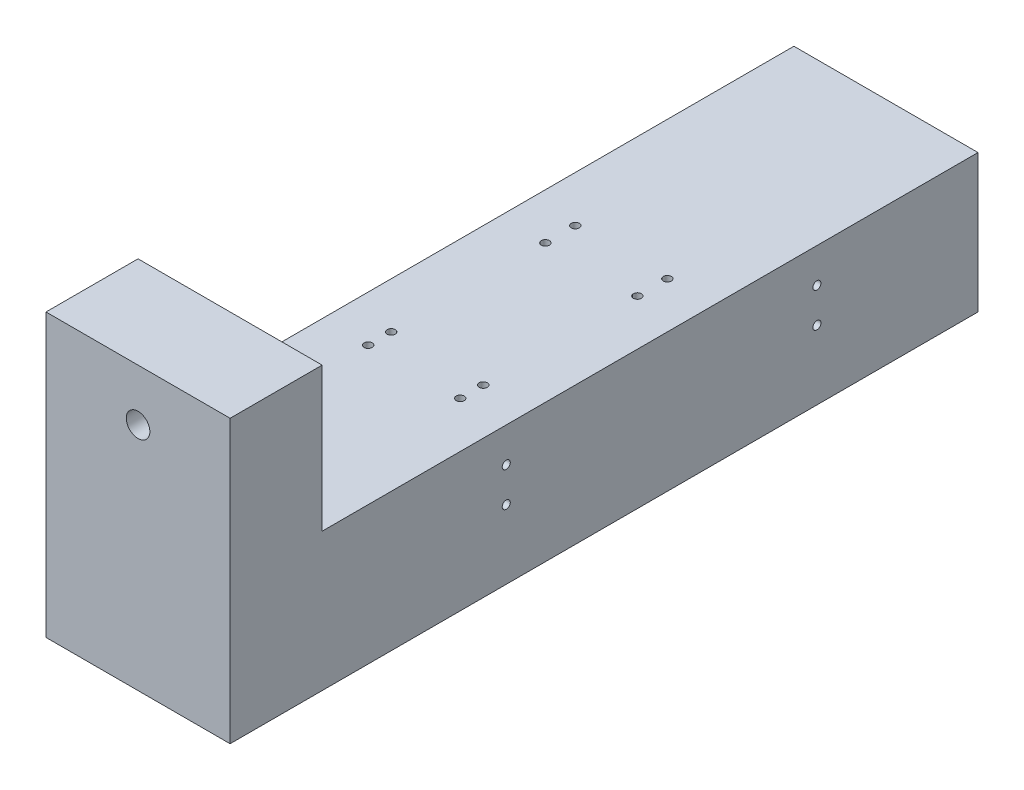
SolidWorks part; units mm, degrees
material "AISI Type A2 Tool Steel"
ref_plane "Front Plane" through (0, 0, 0) normal (0, 0, 1) x (1, 0, 0)
ref_plane "Top Plane" through (0, 0, 0) normal (0, 1, 0) x (1, 0, 0)
ref_plane "Right Plane" through (0, 0, 0) normal (1, 0, 0) x (0, 0, -1)
sketch "Sketch1" plane through (0, 0, 0) normal (0, 0, 1) x (1, 0, 0)
  line L1 (-80, 29.6183) -> (80, 29.6183)
  line L2 (-80, 29.6183) -> (-80, 149.6183)
  line L3 (-80, 149.6183) -> (80, 149.6183)
  line L4 (80, 29.6183) -> (80, 149.6183)
  line L5 (-80, 29.6183) -> (80, 149.6183) construction
  line L6 (-80, 149.6183) -> (80, 29.6183) construction
  point P0 (0, 89.6183)
  dimension "D1" = 160
  dimension "D2" = 120
  dimension "D3" = 89.6183
extrude "Boss-Extrude3" add sketch "Sketch1" along normal blind 570
sketch "Sketch4" plane through (0, 0, 570) normal (0, 0, 1) x (1, 0, 0)
  line L0 (80, 29.6183) -> (80, 149.6183) construction
  line L1 (-80, 29.6183) -> (80, 29.6183)
  line L2 (-80, 29.6183) -> (-80, 274.6183)
  line L3 (-80, 274.6183) -> (80, 274.6183)
  line L4 (80, 29.6183) -> (80, 274.6183)
  line L5 (-80, 29.6183) -> (80, 274.6183) construction
  line L6 (-80, 274.6183) -> (80, 29.6183) construction
  line L7 (-80, 149.6183) -> (-80, 29.6183) construction
  line L8 (-80, 29.6183) -> (80, 29.6183) construction
  point P0 (0, 152.1183)
  dimension "D1" = 245
extrude "Boss-Extrude4" add sketch "Sketch4" along normal blind 80
hole_wizard "Ø20.5 (20.5) Diameter Hole1" positions "Sketch6" profile "Sketch7" hole size "Ø20.5" standard "DIN" end condition through all
sketch "Sketch6" plane through (0, 0, 650) normal (0, 0, 1) x (1, 0, 0)
  line L0 (80, 274.6183) -> (-80, 274.6183) construction
  line L1 (-80, 274.6183) -> (-80, 29.6183) construction
  point P0 (0, 229.6183)
  dimension "D1" = 45
  dimension "D2" = 80
cosmetic thread "Cosmetic Thread1" parameters "D1"=48, "D2"=24
sketch "Sketch7" plane through (0, 229.6183, 650) normal (1, 0, 0) x (0, -1, 0)
  line L0 (0, 0) -> (0, 650)
  line L1 (0, 650) -> (10.25, 650)
  line L2 (10.25, 650) -> (10.25, 0)
  line L5 (10.25, 0) -> (0, 0)
  line L11 (0, -6.35) -> (0, 107.95) construction
  dimension "Thru Hole Dia." = 20.5
  dimension "Thru Hole Depth" = 650
sketch "Sketch8" plane through (0, 149.6183, 0) normal (0, 1, 0) x (1, 0, 0)
  line L0 (0, -0.7396) -> (0, -649.5612) construction
  line L1 (80, -570) -> (80, 0) construction
  line L2 (80, 0) -> (-80, 0) construction
  point P4 (40, -410)
  point P6 (40, -390)
  point P8 (40, -256)
  point P10 (40, -230)
  point P23 (-40, -410)
  point P24 (-40, -390)
  point P25 (-40, -256)
  point P26 (-40, -230)
  dimension "D1" = 80
  dimension "D2" = 26
  dimension "D3" = 40
  dimension "D4" = 40
  dimension "D5" = 40
  dimension "D6" = 40
  dimension "D7" = 20
  dimension "D8" = 230
  dimension "D9" = 390
hole_wizard "M8x1.0 Tapped Hole2" positions "Sketch8" profile "Sketch10" tap size "M8x1.0" standard "ISO"
sketch "Sketch10" plane through (-40, 149.6183, 230) normal (1, 0, 0) x (0, 0, 1)
  line L0 (0, 0) -> (0, 22.103)
  line L1 (0, 22.103) -> (3.5, 20)
  line L2 (3.5, 20) -> (3.5, 0)
  line L5 (3.5, 0) -> (0, 0)
  line L10 (0, 22.103) -> (-3.5, 20) construction
  line L11 (0, -6.35) -> (0, 107.95) construction
  dimension "Tap Drill Dia." = 7
  dimension "Tap Drill Depth" = 20
  dimension "Drill Angle" = 118
cosmetic thread "Hole Thread1" parameters "D1"=16, "D2"=8
cosmetic thread "Hole Thread2" parameters "D1"=16, "D2"=8
cosmetic thread "Hole Thread3" parameters "D1"=16, "D2"=8
cosmetic thread "Hole Thread4" parameters "D1"=16, "D2"=8
cosmetic thread "Hole Thread5" parameters "D1"=16, "D2"=8
cosmetic thread "Hole Thread6" parameters "D1"=16, "D2"=8
cosmetic thread "Hole Thread7" parameters "D1"=16, "D2"=8
cosmetic thread "Hole Thread8" parameters "D1"=16, "D2"=8
hole_wizard "M8x1.0 Tapped Hole3" positions "3DSketch3" profile "Sketch14" tap size "M8x1.0" standard "ISO"
sketch3d "3DSketch3"
  line L0 (80, 29.6183, 0) -> (80, 149.6183, 0) construction
  line L1 (80, 29.6183, 650) -> (80, 29.6183, 0) construction
  point P0 (80, 119.6183, 140)
  point P2 (80, 89.6183, 140)
  point P4 (80, 119.6183, 410)
  point P6 (80, 89.6183, 410)
  dimension "D1" = 30
  dimension "D2" = 30
  dimension "D3" = 140
  dimension "D4" = 60
  dimension "D5" = 60
  dimension "D6" = 410
sketch "Sketch14" plane through (80, 119.6183, 140) normal (0, 1, 0) x (0, 0, -1)
  line L0 (0, 0) -> (0, 22.103)
  line L1 (0, 22.103) -> (3.5, 20)
  line L2 (3.5, 20) -> (3.5, 0)
  line L5 (3.5, 0) -> (0, 0)
  line L10 (0, 22.103) -> (-3.5, 20) construction
  line L11 (0, -6.35) -> (0, 107.95) construction
  dimension "Tap Drill Dia." = 7
  dimension "Tap Drill Depth" = 20
  dimension "Drill Angle" = 118
cosmetic thread "Hole Thread10" parameters "D1"=16, "D2"=8
cosmetic thread "Hole Thread11" parameters "D1"=16, "D2"=8
cosmetic thread "Hole Thread12" parameters "D1"=16, "D2"=8
cosmetic thread "Hole Thread13" parameters "D1"=16, "D2"=8
sketch "Sketch16" plane through (0, 0, 0) normal (0, 1, 0) x (1, 0, 0)
  line L0 (0, -0.0429) -> (0, -648.2423) construction
  dimension "D1" = 0.0429
  dimension "D2" = 648.2423
sketch "Sketch17" plane through (-80, 0, 0) normal (-1, 0, 0) x (0, 0, 1)
  line L0 (650, 29.6183) -> (650, 274.6183) construction
  line L1 (650, 29.6183) -> (0, 29.6183) construction
  line L2 (650, 29.6183) -> (0, 29.6183) construction
  line L3 (650, 274.6183) -> (650, 29.6183) construction
  circle A0 centre (410, 119.6183) radius 3.5 construction
  circle A1 centre (410, 89.6183) radius 3.5 construction
  circle A2 centre (140, 89.6183) radius 3.5 construction
  circle A3 centre (410, 89.6183) radius 3.5 construction
  circle A4 centre (140, 119.6183) radius 3.5 construction
  circle A5 centre (140, 89.6183) radius 3.5 construction
  point P0 (410, 119.6183)
  point P1 (140, 89.6183)
  point P2 (410, 89.6183)
  point P3 (140, 119.6183)
  dimension "D2" = 240
  dimension "D3" = 270
  dimension "D4" = 60
  dimension "D5" = 30
  dimension "D1" = 240
  dimension "D6" = 270
  dimension "D7" = 30
  dimension "D8" = 60
  dimension "D9" = 30
  dimension "D10" = 60
  dimension "D11" = 270
  dimension "D12" = 240
hole_wizard "M8x1.0 Tapped Hole1" positions "Sketch17" profile "Sketch18" tap size "M8x1.0" standard "ISO"
sketch "Sketch18" plane through (-80, 119.6183, 410) normal (0, 1, 0) x (0, 0, 1)
  line L0 (0, 0) -> (0, 22.103)
  line L1 (0, 22.103) -> (3.5, 20)
  line L2 (3.5, 20) -> (3.5, 0)
  line L5 (3.5, 0) -> (0, 0)
  line L10 (0, 22.103) -> (-3.5, 20) construction
  line L11 (0, -6.35) -> (0, 107.95) construction
  dimension "Tap Drill Dia." = 7
  dimension "Tap Drill Depth" = 20
  dimension "Drill Angle" = 118
cosmetic thread "Hole Thread14" parameters "D1"=16, "D2"=8
cosmetic thread "Hole Thread15" parameters "D1"=16, "D2"=8
cosmetic thread "Hole Thread16" parameters "D1"=16, "D2"=8
cosmetic thread "Hole Thread17" parameters "D1"=16, "D2"=8
sketch "Sketch19" plane through (0, 0, 0) normal (0, 0, -1) x (-1, 0, 0)
  line L0 (-80, 149.6183) -> (80, 149.6183) construction
  line L1 (-80, 29.6183) -> (-80, 149.6183) construction
  line L2 (80, 29.6183) -> (-80, 29.6183) construction
  point P0 (-50, 119.6183)
  point P1 (50, 119.6183)
  point P2 (50, 59.6183)
  point P3 (-50, 59.6183)
  dimension "D1" = 30
  dimension "D2" = 30
  dimension "D3" = 30
  dimension "D4" = 60
  dimension "D5" = 30
  dimension "D6" = 100
  dimension "D7" = 100
  dimension "D8" = 60
hole_wizard "M12 Tapped Hole1" positions "Sketch19" profile "Sketch20" tap size "M12" standard "ISO"
sketch "Sketch20" plane through (50, 119.6183, 0) normal (1, 0, 0) x (0, 1, 0)
  line L0 (0, 0) -> (0, 33.0644)
  line L1 (0, 33.0644) -> (5.1, 30)
  line L2 (5.1, 30) -> (5.1, 0)
  line L5 (5.1, 0) -> (0, 0)
  line L10 (0, 33.0644) -> (-5.1, 30) construction
  line L11 (0, -6.35) -> (0, 107.95) construction
  dimension "Tap Drill Dia." = 10.2
  dimension "Tap Drill Depth" = 30
  dimension "Drill Angle" = 118
cosmetic thread "Hole Thread18" parameters "D1"=10.2, "D2"=12
cosmetic thread "Hole Thread19" parameters "D1"=10.2, "D2"=12
cosmetic thread "Hole Thread20" parameters "D1"=10.2, "D2"=12
cosmetic thread "Hole Thread21" parameters "D1"=10.2, "D2"=12
ref_axis "RAM_AXIS" through (0, 229.6183, 570) along (0, 0, 1)
ref_plane "SEAT" through (0, 0, 0) normal (0, 0, -1) x (-1, 0, 0)
ref_plane "HEEL" through (-80, 0, 0) normal (-1, 0, 0) x (0, 0, 1)
ref_axis "Axis2" through (0, 229.6183, 570) along (0, 0, 1)
ref_plane "Plane3" through (0, 0, 0) normal (0, 0, -1) x (-1, 0, 0)
ref_plane "FRONT" through (80, 0, 0) normal (1, 0, 0) x (0, 0, -1)
ref_plane "Plane5" through (-80, 0, 0) normal (-1, 0, 0) x (0, 0, 1)
